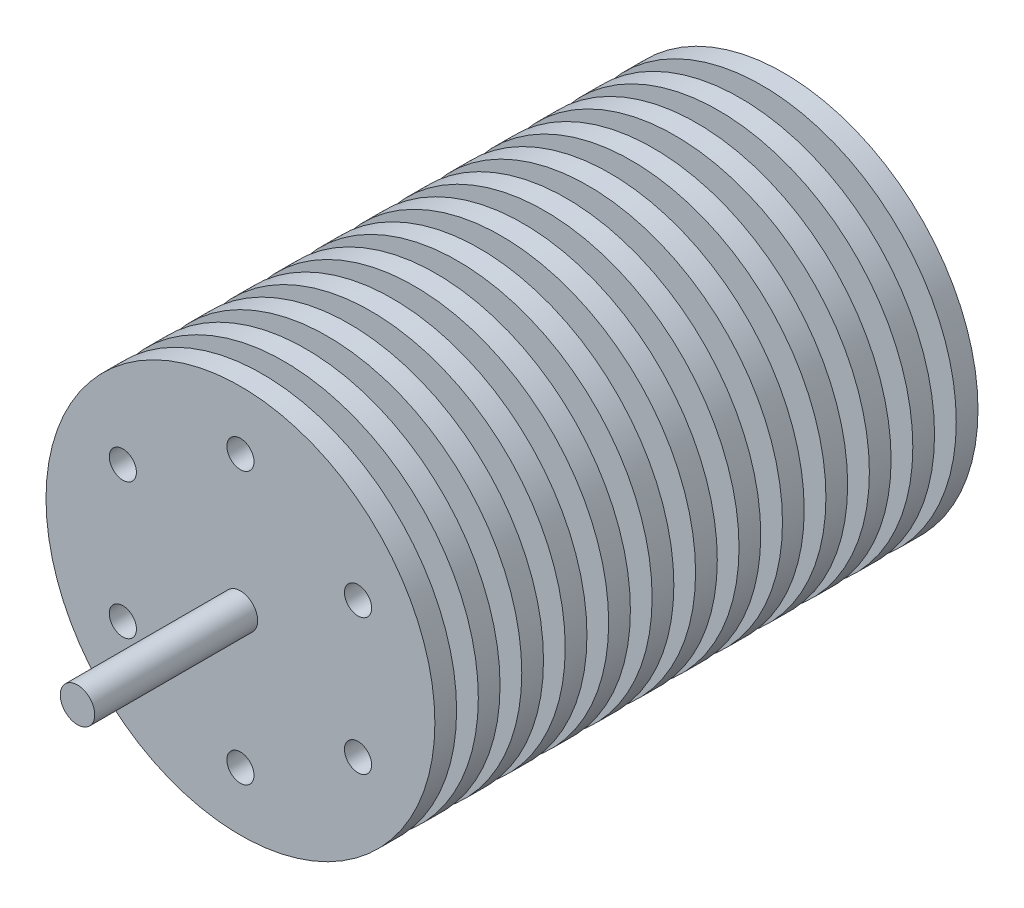
SolidWorks part; units mm, degrees
material "Cast Alloy Steel"
ref_plane "Front Plane" through (0, 0, 0) normal (0, 0, 1) x (1, 0, 0)
ref_plane "Top Plane" through (0, 0, 0) normal (0, 1, 0) x (1, 0, 0)
ref_plane "Right Plane" through (0, 0, 0) normal (1, 0, 0) x (0, 0, -1)
sketch "Sketch1" plane through (0, 0, 0) normal (0, 0, 1) x (1, 0, 0)
  circle A0 centre (0, 0) radius 17.9
  circle A1 centre (0, 0) radius 1.5875
  dimension "D1" = 35.8
  dimension "D2" = 3.175
extrude "Boss-Extrude1" add sketch "Sketch1" along normal blind 50 contours A0
extrude "Boss-Extrude2" add sketch "Sketch1<3>" along normal blind 15 from surface contours A1 starting at face at (17.9, 0, 50)
sketch "Sketch1<3>" plane through (0, 0, 0) normal (0, 0, 1) x (1, 0, 0) same geometry as "Sketch1"
sketch "Sketch2" plane through (0, 0, 50) normal (0, 0, 1) x (1, 0, 0)
  circle A0 centre (0, 0) radius 12.5 construction
  point P3 (0, 12.5)
  point P7 (10.8253, 6.25)
  point P8 (10.8253, -6.25)
  point P9 (0, -12.5)
  point P10 (-10.8253, -6.25)
  point P11 (-10.8253, 6.25)
  point P12 (0, 0)
  dimension "D1" = 25
  dimension "D2" = 6
hole_wizard "Tap Drill for M3 Tap1" positions "Sketch3" profile "Sketch5" hole size "M3" standard "ISO"
sketch "Sketch3" plane through (0, 0, 50) normal (0, 0, 1) x (1, 0, 0)
  point P0 (0, 12.5)
  point P3 (10.8253, 6.25)
  point P6 (10.8253, -6.25)
  point P9 (0, -12.5)
  point P12 (-10.8253, -6.25)
  point P15 (-10.8253, 6.25)
sketch "Sketch5" plane through (0, 12.5, 50) normal (1, 0, 0) x (0, -1, 0)
  line L0 (0, 0) -> (0, 5.7511)
  line L1 (0, 5.7511) -> (1.25, 5)
  line L2 (1.25, 5) -> (1.25, 0)
  line L5 (1.25, 0) -> (0, 0)
  line L10 (0, 5.7511) -> (-1.25, 5) construction
  line L11 (0, -6.35) -> (0, 107.95) construction
  dimension "Hole Dia." = 2.5
  dimension "Hole Depth" = 5
  dimension "Drill Angle" = 118
sketch "Sketch6" plane through (0, 0, 0) normal (1, 0, 0) x (0, 0, -1)
  line L5 (0, 17.9) -> (-50, 17.9) construction
  line L6 (-48, 17.9) -> (-46, 17.9)
  line L7 (-48, 17.9) -> (-48, 14.9)
  line L8 (-48, 14.9) -> (-46, 14.9)
  line L9 (-46, 17.9) -> (-46, 14.9)
  line L10 (-50, 17.9) -> (-50, -17.9) construction
  line L11 (-44, 17.9) -> (-44, 14.9)
  line L12 (-44, 17.9) -> (-42, 17.9)
  line L13 (-42, 17.9) -> (-42, 14.9)
  line L14 (-44, 14.9) -> (-42, 14.9)
  line L15 (-40, 17.9) -> (-40, 14.9)
  line L16 (-40, 17.9) -> (-38, 17.9)
  line L17 (-38, 17.9) -> (-38, 14.9)
  line L18 (-40, 14.9) -> (-38, 14.9)
  line L19 (-36, 17.9) -> (-36, 14.9)
  line L20 (-36, 17.9) -> (-34, 17.9)
  line L21 (-34, 17.9) -> (-34, 14.9)
  line L22 (-36, 14.9) -> (-34, 14.9)
  line L23 (-32, 17.9) -> (-32, 14.9)
  line L24 (-32, 17.9) -> (-30, 17.9)
  line L25 (-30, 17.9) -> (-30, 14.9)
  line L26 (-32, 14.9) -> (-30, 14.9)
  line L27 (-28, 17.9) -> (-28, 14.9)
  line L28 (-28, 17.9) -> (-26, 17.9)
  line L29 (-26, 17.9) -> (-26, 14.9)
  line L30 (-28, 14.9) -> (-26, 14.9)
  line L31 (-24, 17.9) -> (-24, 14.9)
  line L32 (-24, 17.9) -> (-22, 17.9)
  line L33 (-22, 17.9) -> (-22, 14.9)
  line L34 (-24, 14.9) -> (-22, 14.9)
  line L35 (-20, 17.9) -> (-20, 14.9)
  line L36 (-20, 17.9) -> (-18, 17.9)
  line L37 (-18, 17.9) -> (-18, 14.9)
  line L38 (-20, 14.9) -> (-18, 14.9)
  line L39 (-16, 17.9) -> (-16, 14.9)
  line L40 (-16, 17.9) -> (-14, 17.9)
  line L41 (-14, 17.9) -> (-14, 14.9)
  line L42 (-16, 14.9) -> (-14, 14.9)
  line L43 (-12, 17.9) -> (-12, 14.9)
  line L44 (-12, 17.9) -> (-10, 17.9)
  line L45 (-10, 17.9) -> (-10, 14.9)
  line L46 (-12, 14.9) -> (-10, 14.9)
  line L47 (-8, 17.9) -> (-8, 14.9)
  line L48 (-8, 17.9) -> (-6, 17.9)
  line L49 (-6, 17.9) -> (-6, 14.9)
  line L50 (-8, 14.9) -> (-6, 14.9)
  line L51 (-4, 17.9) -> (-4, 14.9)
  line L52 (-4, 17.9) -> (-2, 17.9)
  line L53 (-2, 17.9) -> (-2, 14.9)
  line L54 (-4, 14.9) -> (-2, 14.9)
  dimension "D1" = 2
  dimension "D2" = 3
  dimension "D3" = 2
  dimension "D5" = 2
  dimension "D4" = 12
ref_axis "Axis1" through (0, 0, -3.25) along (0, 0, 1)
revolve "Cut-Revolve1" cut sketch "Sketch6" angle 360 about axis through (0, 0, -3.25) along (0, 0, 1)
